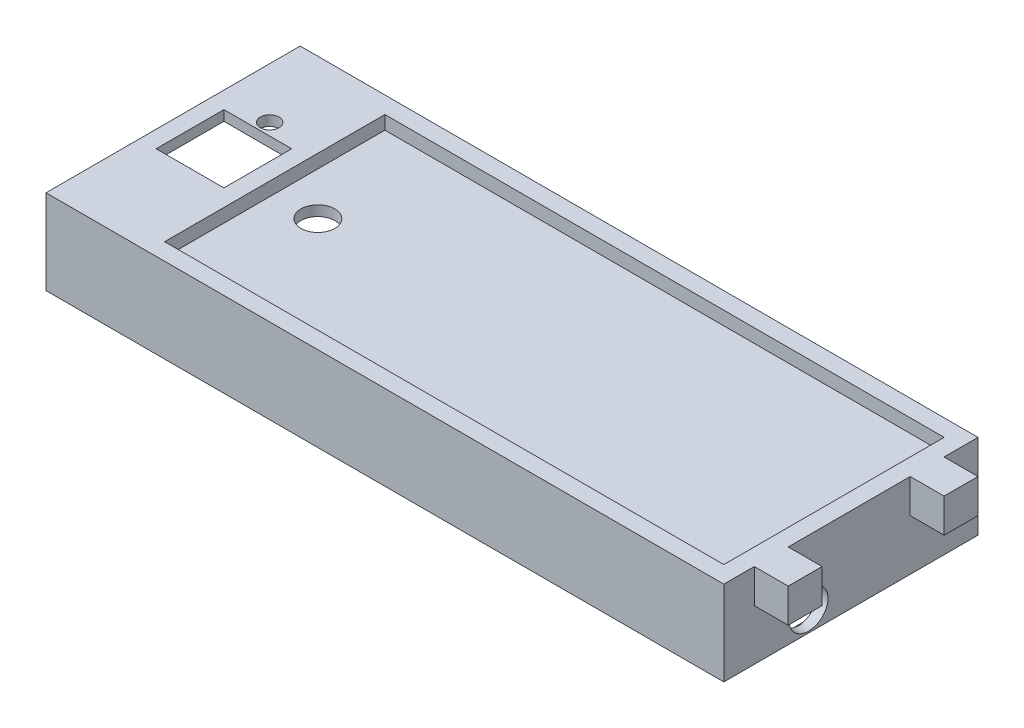
SolidWorks part; units mm, degrees
ref_plane "Front Plane" through (0, 0, 0) normal (0, 0, 1) x (1, 0, 0)
ref_plane "Top Plane" through (0, 0, 0) normal (0, 1, 0) x (1, 0, 0)
ref_plane "Right Plane" through (0, 0, 0) normal (1, 0, 0) x (0, 0, -1)
sketch "Sketch1" plane through (0, 0, 0) normal (0, 1, 0) x (1, 0, 0)
  line L1 (-60, 37.5) -> (140, 37.5)
  line L2 (-60, 37.5) -> (-60, -37.5)
  line L3 (-60, -37.5) -> (140, -37.5)
  line L4 (140, 37.5) -> (140, -37.5)
  point P0 (0, 0)
  dimension "D1" = 200
  dimension "D2" = 75
extrude "Boss-Extrude1" add sketch "Sketch1" along normal blind 25
sketch "Sketch9" plane through (0, 25, 0) normal (0, 1, 0) x (1, 0, 0)
  line L1 (-30, 32.5) -> (135, 32.5)
  line L2 (-30, 32.5) -> (-30, -32.5)
  line L3 (-30, -32.5) -> (135, -32.5)
  line L4 (135, 32.5) -> (135, -32.5)
  line L5 (140, -37.5) -> (140, 37.5) construction
  point P4 (135, 0)
  dimension "D1" = 165
  dimension "D2" = 65
  dimension "D3" = 0
  dimension "D4" = 5
extrude "Cut-Extrude5" cut sketch "Sketch9" against normal blind 4
shell "Shell3" thickness 3 removed face at (40, 0, 0) removed face at (-60, 12.5, 0)
sketch "Sketch14" plane through (140, 0, 0) normal (1, 0, 0) x (0, 0, -1)
  line L0 (37.5, 25) -> (37.5, 0) construction
  line L1 (-28.5, 25) -> (-18.5, 25)
  line L2 (-28.5, 25) -> (-28.5, 15)
  line L3 (-28.5, 15) -> (-18.5, 15)
  line L4 (-18.5, 25) -> (-18.5, 15)
  line L5 (17.5, 25) -> (27.5, 25)
  line L6 (17.5, 25) -> (17.5, 15)
  line L7 (17.5, 15) -> (27.5, 15)
  line L8 (27.5, 25) -> (27.5, 15)
  line L9 (-37.5, 25) -> (37.5, 25) construction
  dimension "D1" = 10
  dimension "D2" = 10
  dimension "D3" = 10
  dimension "D4" = 36
extrude "Boss-Extrude5" add sketch "Sketch14" along normal blind 10
sketch "Sketch15" plane through (0, 21, 0) normal (0, 1, 0) x (1, 0, 0)
  circle A0 centre (-17.2823, 0) radius 5
extrude "Cut-Extrude7" cut sketch "Sketch15" against normal through all
sketch "Sketch16" plane through (0, 25, 0) normal (0, 1, 0) x (1, 0, 0)
  line L0 (-30, 32.5) -> (-30, -32.5) construction
  line L1 (-55, -10) -> (-35, -10)
  line L2 (-55, -10) -> (-55, 10)
  line L3 (-55, 10) -> (-35, 10)
  line L4 (-35, -10) -> (-35, 10)
  line L5 (-55, -10) -> (-35, 10) construction
  line L6 (-55, 10) -> (-35, -10) construction
  line L7 (-60, -37.5) -> (140, -37.5) construction
  line L8 (140, 37.5) -> (-60, 37.5) construction
  point P0 (-45, 0)
  dimension "D1" = 20
  dimension "D2" = 20
  dimension "D3" = 5
  dimension "D4" = 27.5
  dimension "D5" = 27.5
extrude "Cut-Extrude8" cut sketch "Sketch16" against normal through all
ref_plane "Plane1" through (0, 0, 0) normal (0, 0, -1) x (-1, 0, 0)
sketch "Sketch19" plane through (140, 0, 0) normal (1, 0, 0) x (0, 0, -1)
  line L1 (-37.5, 0) -> (37.5, 0) construction
  line L3 (-37.5, 25) -> (-37.5, 0) construction
  ellipse E0 centre (-12.5, 6) end of major axis (-6.75, 6) minor radius 5.5
  dimension "D1" = 6
  dimension "D2" = 25
  dimension "D3" = 11.5
  dimension "D4" = 11
sketch "Sketch20" plane through (0, 0, 0) normal (0, 0, -1) x (-1, 0, 0)
  line L1 (-137, 18) -> (-137, 0) construction
  spline S0 degree 2 poles (-140, 6) (-136.1989, 6.6303) (-133.0758, 4.1829) knots 0 0 0 1 1 1
sweep "Cut-Sweep2" cut profiles "Sketch19" path "Sketch20"
sketch "Sketch21" plane through (0, 25, 0) normal (0, 1, 0) x (1, 0, 0)
  line L0 (-55, 0) -> (-35, 0)
  line L1 (-55, 10) -> (-55, -10) construction
  line L2 (-35, -10) -> (-35, 10) construction
  line L3 (-45, 0) -> (-45, 13.5)
  circle A0 centre (-45, 13.5) radius 2.75
  dimension "D2" = 5.5
  dimension "D1" = 13.5
extrude "Cut-Extrude9" cut sketch "Sketch21" against normal through all contours A0
sketch3d "3DSketch1"
  line L0 (-60, 0, 34.5) -> (-60, 6, 34.5) construction
  line L1 (-60, 22, 34.5) -> (-60, 0, 34.5) construction
  line L2 (-60, 6, 34.5) -> (-60, 6, 32.7) construction
  line L3 (-60, 6, 32.7) -> (-56.4756, 6, 32.7) construction
  line L4 (-56.4756, 6, 32.7) -> (126.5244, 6, 32.7) construction
  line L5 (126.5244, 6, 32.7) -> (131.5244, 6, 32.7) construction
  line L6 (131.5244, 6, 32.7) -> (131.5244, 6, 27.5033) construction
  line L7 (131.5244, 6, 27.5033) -> (131.5244, 6, 16.563) construction
  line L8 (-60, 6, 32.7) -> (-60, 6, 27.3188) construction
  line L9 (-60, 6, 27.3188) -> (-60, 6, 27.5805)
  line L10 (-60, 6, 27.5805) -> (-60, 6, -4.2159)
  dimension "D2" = 1.8
  dimension "D1" = 6
  dimension "183" = 183
  dimension "D3" = 5
ref_axis "Axis1" through (-56.4756, 6, 32.7) along (1, 0, 0)
other "RPoint1"
other "RPoint2"
ref_axis "Axis2" through (131.5244, 6, 27.5033) along (0, 0, -1)
other "RPoint3"
other "RPoint4"
ref_axis "Axis3" through (-60, 6, 27.5805) along (0, 0, -1)
other "RPoint5"
other "RPoint6"
